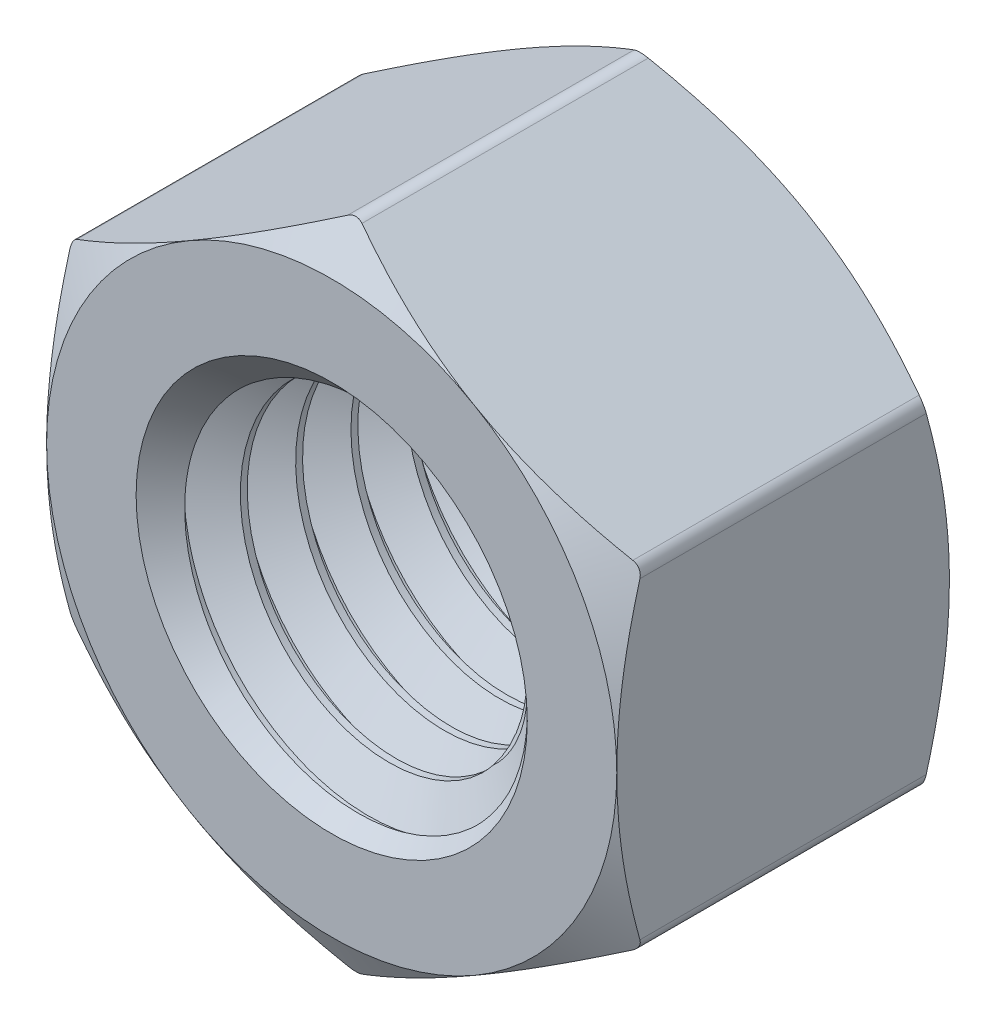
SolidWorks part; units mm, degrees
ref_plane "Front" through (0, 0, 0) normal (0, 0, 1) x (1, 0, 0)
ref_plane "Top" through (0, 0, 0) normal (0, 1, 0) x (1, 0, 0)
ref_plane "Right" through (0, 0, 0) normal (1, 0, 0) x (0, 0, -1)
sketch "Sketch1" plane through (0, 0, 0) normal (0, 0, 1) x (1, 0, 0)
  line L0 (0, 7.9375) -> (0, 5.6284) construction
  line L1 (-11.9062, 6.8741) -> (-11.9062, -6.8741)
  line L2 (-11.9062, -6.8741) -> (0, -13.7482)
  line L3 (0, -13.7482) -> (11.9062, -6.8741)
  line L4 (11.9062, -6.8741) -> (11.9062, 6.8741)
  line L5 (11.9062, 6.8741) -> (0, 13.7482)
  line L6 (0, 13.7482) -> (-11.9062, 6.8741)
  circle A0 centre (0, 0) radius 11.9062 construction
  circle A1 centre (0, 0) radius 7.9375 construction
  point P10 (0, 7.9375)
  dimension "Width" = 23.8125
  dimension "Thread Size" = 15.875
  dimension "Thread Pitch" = 2.3091
sketch "Sketch2" plane through (0, 0, 0) normal (1, 0, 0) x (0, 0, -1)
  line L0 (-6.9453, 0) -> (6.9453, 0) construction
  line L1 (-6.9453, 13.7482) -> (6.9453, 13.7482) construction
  dimension "Height" = 13.8906
sketch "Sketch15" plane through (0, 0, 0) normal (0, 0, 1) x (1, 0, 0)
  line L1 (0, 13.7482) -> (-11.9063, 6.8741)
  line L2 (-11.9063, 6.8741) -> (-11.9063, -6.8741)
  line L3 (-11.9063, -6.8741) -> (0, -13.7482)
  line L4 (0, -13.7482) -> (11.9062, -6.8741)
  line L5 (11.9062, -6.8741) -> (11.9062, 6.8741)
  line L6 (11.9062, 6.8741) -> (0, 13.7482)
  circle A0 centre (0, 0) radius 11.9063 construction
extrude "Boss-Extrude2" add sketch "Sketch15" along normal mid plane 13.8906
sketch "Sketch16" plane through (0, 0, 0) normal (0, 0, 1) x (1, 0, 0)
  circle A0 centre (0, 0) radius 7.9375 construction
  circle A1 centre (0, 0) radius 7.9375
sketch "Sketch4" plane through (0, 0, -6.9453) normal (0, 0, -1) x (-1, 0, 0)
  circle A0 centre (0, 0) radius 7.9375 construction
  circle A1 centre (0, 0) radius 7.9375
extrude "Cut-Extrude4" cut sketch "Sketch16" against normal through all both and the other way through all
sketch "Sketch7" plane through (0, 0, 6.9453) normal (0, 0, 1) x (1, 0, 0)
  circle A0 centre (0, 0) radius 11.9062 construction
  circle A1 centre (0, 0) radius 11.9062
extrude "Cut-Extrude5" cut sketch "Sketch7" against normal through all draft 60 flip side to cut
mirror "Mirror4" about plane through (0, 0, 0) normal (0, 0, 1) of "Cut-Extrude5"
fillet "Fillet2" radius 0.5953 6 edges at (-11.9063, 6.8741, 0) (-11.9063, -6.8741, 0) (0, -13.7482, 0) (11.9062, -6.8741, 0) (11.9062, 6.8741, 0) (0, 13.7482, 0)
sketch "Sketch8" plane through (0, 0, 6.9453) normal (0, 0, 1) x (1, 0, 0)
  line L0 (2.0544, -7.667) -> (0, 0) construction
  line L2 (0, 7.9375) -> (0, 5.6284) construction
  circle A0 centre (0, 0) radius 7.9375 construction
  point P0 (2.0544, -7.667)
  dimension "D1" = 15
sketch "Sketch13" plane through (0, 0, -6.9453) normal (0, 0, -1) x (-1, 0, 0)
  circle A0 centre (0, 0) radius 7.9375 construction
  circle A1 centre (0, 0) radius 7.9375
extrude "Boss-Extrude1" add sketch "Sketch13" against normal up to surface (13.8906 mm away) separate body up to face at (7.9375, 0, 6.9453)
curve "Helix/Spiral3" pitch 2.3091 height 16.1997 radius 7.9375 centre (0, 0, -6.9453) axis (0, 0, 1) start towards (0, 1, 0)
sketch "Sketch12" plane through (0, 0, 0) normal (1, 0, 0) x (0, 0, -1)
  line L0 (8.9658, 7.9375) -> (6.9453, 7.9375)
  line L1 (8.9658, 7.9375) -> (8.0999, 6.4377)
  line L2 (8.0999, 6.4377) -> (7.8112, 6.4377)
  line L3 (7.8112, 6.4377) -> (6.9453, 7.9375)
  line L4 (7.9555, 6.4377) -> (7.9555, 7.9375) construction
  line L5 (7.3783, 7.1876) -> (8.5328, 7.1876) construction
  dimension "D1" = 60
  dimension "D2" = 0.2886
  dimension "D3" = 1.1545
sweep "Cut-Sweep1" cut profiles "Sketch12" path "Helix/Spiral3" align with end faces yes
sketch "Sketch17" plane through (0, 0, 6.9453) normal (0, 0, 1) x (1, 0, 0)
  circle A1 centre (0, 0) radius 7.9375
  circle A2 centre (0, 0) radius 7.9375
  dimension "D1" = 0
extrude "Boss-Extrude3" add sketch "Sketch17" against normal up to surface (13.8906 mm away) up to face at (7.9375, 0, -6.9453)
combine bodies "Combine1" operation type subtract main body 127 bodies to subtract 118
sketch "Sketch10" plane through (0, 0, 6.9453) normal (0, 0, 1) x (1, 0, 0)
  circle A0 centre (0, 0) radius 7.9375 construction
  circle A1 centre (0, 0) radius 7.9375 construction
  circle A2 centre (0, 0) radius 8.1684
  dimension "D1" = 0.2309
extrude "Cut-Extrude2" cut sketch "Sketch10" against normal through all draft 45
sketch "Sketch11" plane through (0, 0, -6.9453) normal (0, 0, -1) x (-1, 0, 0)
  circle A1 centre (0, 0) radius 8.1684 construction
  circle A2 centre (0, 0) radius 8.1684
extrude "Cut-Extrude3" cut sketch "Sketch11" against normal through all draft 45
equation "\"D1\"= \"Height@Sketch2\""
equation "\"D3@Helix/Spiral3\"=\"Height@Sketch2\"+\"Thread Pitch@Sketch1\""
equation "\"D4@Helix/Spiral3\"=\"Thread Pitch@Sketch1\""
equation "\"D2@Sketch12\" = \"D4@Helix/Spiral3\"*.125"
equation "\"D3@Sketch12\" = \"D4@Helix/Spiral3\"*.50"
equation "\"D1@Boss-Extrude2\"=\"Height@Sketch2\""
equation "\"D1@Fillet2\"=\"Width@Sketch1\"*0.025"
equation "\"D1@Sketch10\"=\"Thread Pitch@Sketch1\"*0.1"
